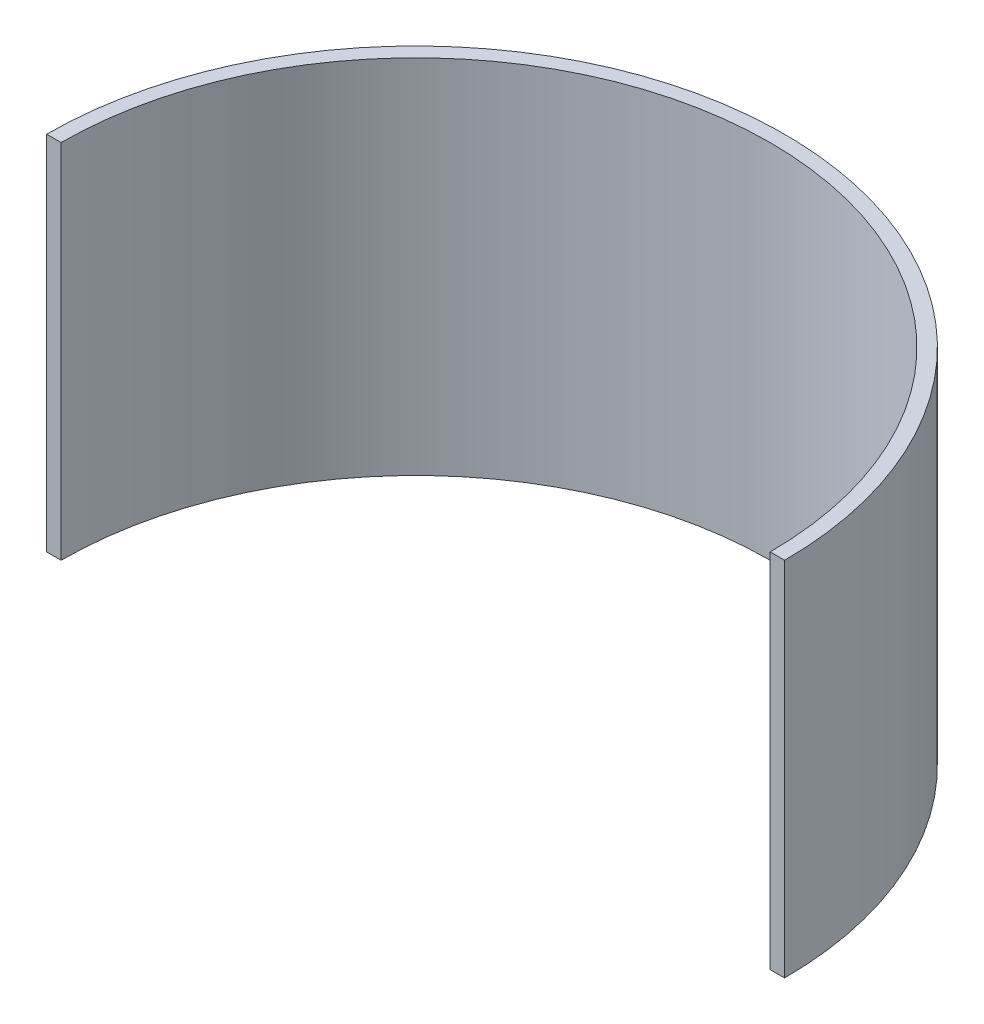
SolidWorks part; units mm, degrees
ref_plane "Front Plane" through (0, 0, 0) normal (0, 0, 1) x (1, 0, 0)
ref_plane "Top Plane" through (0, 0, 0) normal (0, 1, 0) x (1, 0, 0)
ref_plane "Right Plane" through (0, 0, 0) normal (1, 0, 0) x (0, 0, -1)
sketch "Sketch1" plane through (0, 0, 0) normal (0, 1, 0) x (1, 0, 0)
  line L0 (-102, 0) -> (-98, 0)
  line L1 (98, 0) -> (102, 0)
  arc A0 (-98, 0) -> (98, 0) centre (0, 0) cw
  arc A1 (-102, 0) -> (102, 0) centre (0, 0) cw
  dimension "D1" = 98
  dimension "D2" = 4
extrude "Boss-Extrude1" add sketch "Sketch1" along normal blind 100
